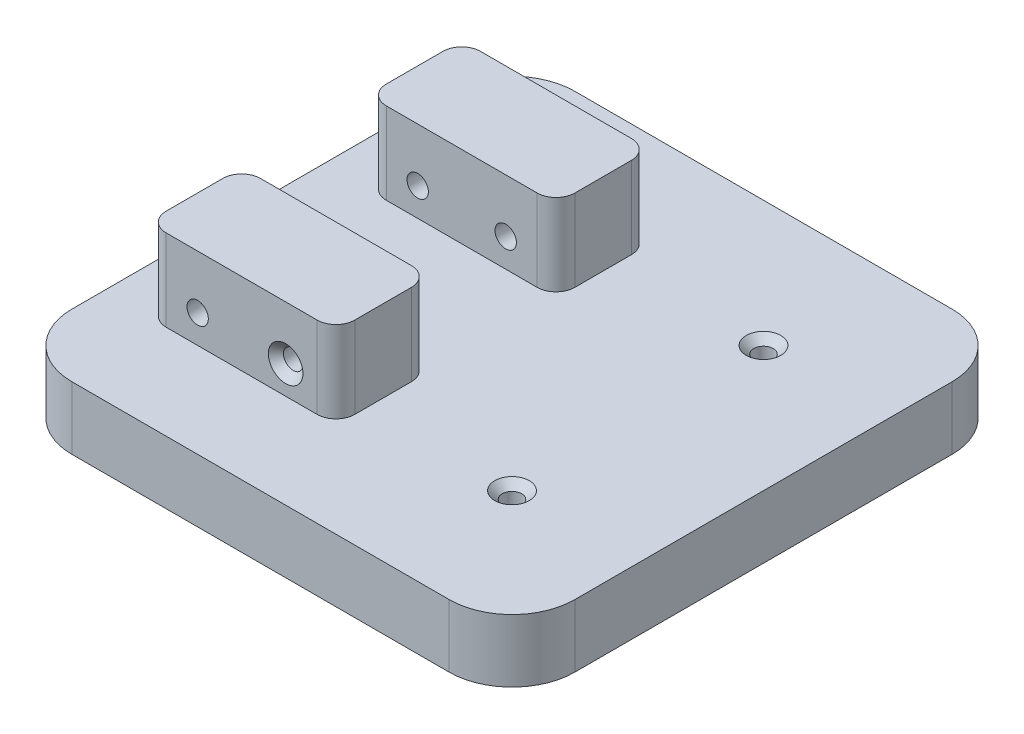
SolidWorks part; units mm, degrees
ref_plane "Piano frontale" through (0, 0, 0) normal (0, 0, 1) x (1, 0, 0)
ref_plane "Piano superiore" through (0, 0, 0) normal (0, 1, 0) x (1, 0, 0)
ref_plane "Piano destro" through (0, 0, 0) normal (1, 0, 0) x (0, 0, -1)
sketch "Schizzo1" plane through (0, 0, 0) normal (0, 1, 0) x (1, 0, 0)
  line L0 (-47.6, 35.6) -> (-47.6, -44.4)
  line L1 (-47.6, 35.6) -> (32.4, 35.6)
  line L2 (32.4, 35.6) -> (32.4, -44.4)
  line L3 (32.4, -44.4) -> (-47.6, -44.4)
  dimension "D1" = 80
  dimension "D2" = 80
extrude "Estrusione-Estrusione1" add sketch "Schizzo1" along normal blind 10
fillet "Raccordo1" radius 10 4 edges at (-47.6, 5, -35.6) (32.4, 5, -35.6) (-47.6, 5, 44.4) (32.4, 5, 44.4)
sketch "Schizzo2" plane through (0, 10, 0) normal (0, 1, 0) x (1, 0, 0)
  line L0 (12.4, -44.4) -> (12.4, 35.6) construction
  line L1 (-37.6, -44.4) -> (22.4, -44.4) construction
  line L2 (22.4, 35.6) -> (-37.6, 35.6) construction
  line L3 (-47.6, 25.6) -> (-47.6, -34.4) construction
  line L4 (12.4, -4.4) -> (-47.6, -4.4) construction
  line L5 (12.4, 15.6) -> (-47.6, 15.6) construction
  line L7 (12.4, -24.4) -> (-47.6, -24.4) construction
  dimension "D1" = 60
  dimension "D2" = 20
  dimension "D3" = 20
hole_wizard "Foro svasato per Vite M2.5-1" positions "Schizzo3D1" profile "Schizzo3" countersink size "M2.5" standard "IS" end condition through all
sketch3d "Schizzo3D1"
  point P0 (12.4, 10, -15.6)
  point P3 (12.4, 10, 24.4)
sketch "Schizzo3" plane through (12.4, 10, -15.6) normal (1, 0, 0) x (0, 0, 1)
  line L0 (0, 0) -> (0, 10)
  line L1 (0, 10) -> (1.55, 10)
  line L2 (1.55, 10) -> (1.55, 1.2)
  line L3 (1.55, 1.2) -> (2.75, 0)
  line L5 (2.75, 0) -> (0, 0)
  line L6 (-1.55, 1.2) -> (-2.75, 0) construction
  line L11 (0, -6.35) -> (0, 107.95) construction
  dimension "Thru Hole Dia." = 3.1
  dimension "Thru Hole Depth" = 10
  dimension "Near C'Sink Dia." = 5.5
  dimension "Near C'Sink Angle" = 90
sketch "Schizzo4" plane through (0, 10, 0) normal (0, 1, 0) x (1, 0, 0)
  line L0 (-40.6, 20.6) -> (-40.6, 5.6)
  line L1 (-40.6, 5.6) -> (-10.6, 5.6)
  line L2 (-10.6, 5.6) -> (-10.6, 20.6)
  line L3 (-10.6, 20.6) -> (-40.6, 20.6)
  line L4 (-10.6, -14.4) -> (-10.6, -29.4)
  line L5 (-10.6, -29.4) -> (-40.6, -29.4)
  line L6 (-40.6, -29.4) -> (-40.6, -14.4)
  line L7 (-40.6, -14.4) -> (-10.6, -14.4)
  line L8 (-47.6, -4.4) -> (32.4, -4.4) construction
  line L10 (-47.6, 25.6) -> (-47.6, -34.4) construction
  line L11 (32.4, -34.4) -> (32.4, 25.6) construction
  dimension "D1" = 15
  dimension "D2" = 15
  dimension "D3" = 10
  dimension "D4" = 10
  dimension "D5" = 7
  dimension "D6" = 30
  dimension "D7" = 30
extrude "Estrusione-Estrusione2" add sketch "Schizzo4" along normal blind 13
sketch "Schizzo5" plane through (0, 0, -20.6) normal (0, 0, -1) x (-1, 0, 0)
  line L0 (40.6, 14.5) -> (10.6, 14.5) construction
  line L1 (10.6, 23) -> (10.6, 10) construction
  line L2 (18.6, 10) -> (18.6, 23) construction
  line L3 (-12.4, 10) -> (47.6, 10) construction
  line L4 (10.6, 23) -> (40.6, 23) construction
  line L6 (32.6, 10) -> (32.6, 23) construction
  line L7 (40.6, 23) -> (40.6, 10) construction
  circle A0 centre (18.6, 14.5) radius 1.7
  circle A1 centre (32.6, 14.5) radius 1.7
  dimension "D4" = 3.4
  dimension "D5" = 3.4
  dimension "D6" = 14
  dimension "D1" = 4.5
  dimension "D2" = 8
  dimension "D3" = 8
sketch "Schizzo6" plane through (0, 0, 29.4) normal (0, 0, 1) x (1, 0, 0)
  line L0 (-40.6, 14.5) -> (-10.6, 14.5) construction
  line L1 (-37.6, 10) -> (22.4, 10) construction
  line L2 (-18.6, 23) -> (-18.6, 10) construction
  line L4 (-32.6, 23) -> (-32.6, 10) construction
  circle A0 centre (-32.6, 14.5) radius 1.7
  dimension "D2" = 3.4
  dimension "D1" = 4.5
hole_wizard "Foro svasato per Vite M2.5-2" positions "Schizzo3D4" profile "Schizzo10" countersink size "M2.5" standard "IS"
sketch3d "Schizzo3D4"
  line L0 (-40.6, 14.5, 29.4) -> (-10.6, 14.5, 29.4) construction
  line L1 (-18.6, 23, 29.4) -> (-18.6, 10, 29.4) construction
  point P0 (-18.6, 14.5, 29.4)
sketch "Schizzo10" plane through (-18.6, 14.5, 29.4) normal (1, 0, 0) x (0, -1, 0)
  line L0 (0, 0) -> (0, 15.9313)
  line L1 (0, 15.9313) -> (1.55, 15)
  line L2 (1.55, 15) -> (1.55, 1.2)
  line L3 (1.55, 1.2) -> (2.75, 0)
  line L5 (2.75, 0) -> (0, 0)
  line L6 (-1.55, 1.2) -> (-2.75, 0) construction
  line L10 (0, 15.9313) -> (-1.55, 15) construction
  line L11 (0, -6.35) -> (0, 107.95) construction
  dimension "Hole Dia." = 3.1
  dimension "Hole Depth" = 15
  dimension "Near C'Sink Dia." = 5.5
  dimension "Near C'Sink Angle" = 90
  dimension "Drill Angle" = 118
fillet "Raccordo2" radius 3 8 edges at (-10.6, 16.5, -20.6) (-10.6, 16.5, -5.6) (-40.6, 16.5, -20.6) (-40.6, 16.5, -5.6) (-10.6, 16.5, 29.4) (-10.6, 16.5, 14.4) (-40.6, 16.5, 14.4) (-40.6, 16.5, 29.4)
extrude "Taglio-Estrusione4" cut sketch "Schizzo5" against normal blind 15
extrude "Taglio-Estrusione5" cut sketch "Schizzo6" against normal blind 15
sketch "Schizzo12" plane through (0, 0, -5.6) normal (0, 0, 1) x (1, 0, 0)
  line L0 (-37.6, 10) -> (-13.6, 10) construction
  line L1 (-32.6, 12.8) -> (-32.6, 10) construction
  line L2 (-25.6, 8.0069) -> (-25.6, 23) construction
  line L3 (-37.6, 23) -> (-13.6, 23) construction
  line L5 (-18.6, 12.8) -> (-18.6, 10) construction
  circle A0 centre (-32.6, 14.5) radius 1.7 construction
  circle A1 centre (-18.6, 14.5) radius 1.7 construction
  dimension "D1" = 14
